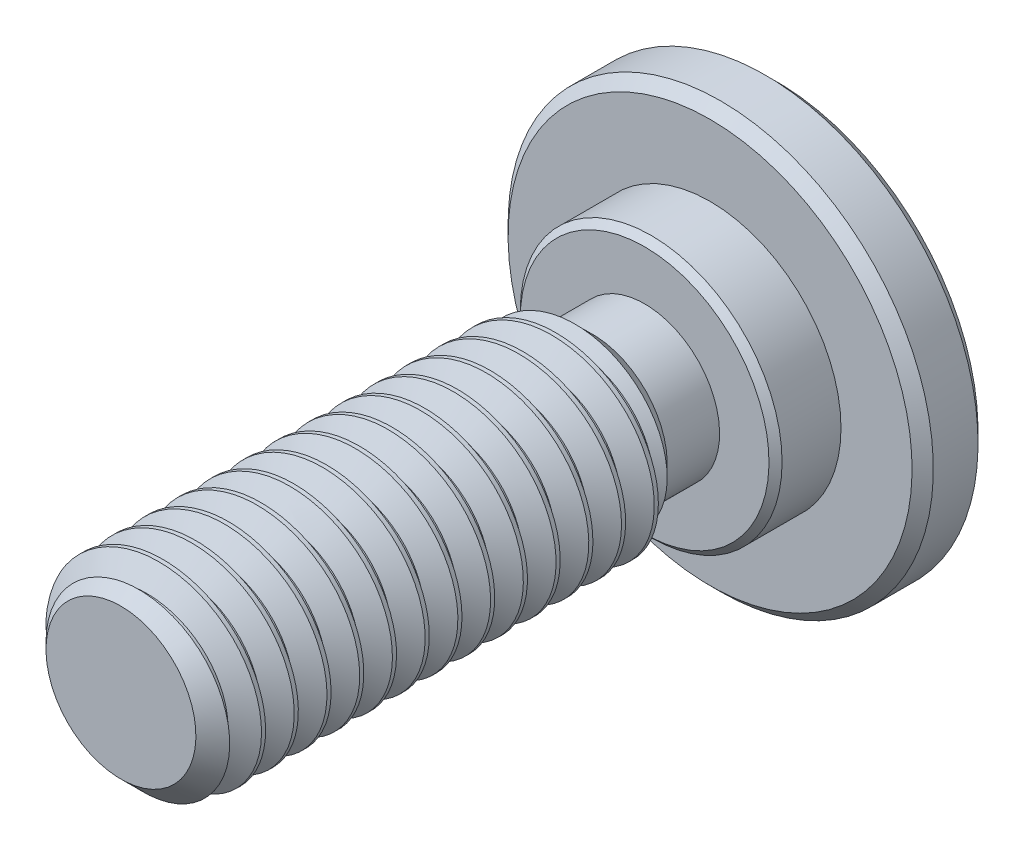
SolidWorks part; units mm, degrees
other "DetailItem1"
ref_plane "Front Plane" through (0, 0, 0) normal (0, 0, 1) x (1, 0, 0)
ref_plane "Top Plane" through (0, 0, 0) normal (0, 1, 0) x (1, 0, 0)
ref_plane "Right Plane" through (0, 0, 0) normal (1, 0, 0) x (0, 0, -1)
sketch "Sketch1" plane through (0, 0, 0) normal (1, 0, 0) x (0, 0, -1)
  line L0 (0, 0) -> (-14.2875, 0) construction
  line L1 (0, 0) -> (1.6002, 0) construction
  line L2 (1.6002, 5.1562) -> (1.6002, -5.1562) construction
  line L3 (-14.2875, 2.413) -> (-14.2875, -2.413) construction
  line L4 (0, 3.175) -> (0, -3.175) construction
  line L5 (-14.2875, 2.413) -> (-13.4938, 2.413) construction
  line L6 (1.6002, 1.1906) -> (1.6002, -1.1906) construction
  line L7 (0, 3.175) -> (-1.5875, 3.175) construction
  line L8 (-1.5875, 3.175) -> (-1.5875, 1.8177) construction
  line L9 (-1.5875, 1.8177) -> (-2.8575, 1.8177) construction
  line L10 (-2.8575, 1.8177) -> (-3.4528, 2.413) construction
  point P2 (-11.5094, -2.413)
  point P4 (-1.5875, 0)
  point P8 (1.6002, 0)
  point P11 (-14.2875, 0)
  point P14 (0, 0)
  point P19 (1.6002, 0)
  dimension "Thread Diameter" = 4.826
  dimension "Head Diameter" = 10.3124
  dimension "Head Height" = 1.6002
  dimension "Shoulder Diameter" = 6.35
  dimension "Shoulder Length" = 1.5875
  dimension "Thread Pitch" = 0.7937
  dimension "Drive Size" = 2.3813
  dimension "D1" = 2.7781
  dimension "D3" = 3.6354
  dimension "Undercut Length" = 1.27
  dimension "D2" = 45
  dimension "Length" = 12.7
sketch "Sketch13" plane through (0, 0, 0) normal (1, 0, 0) x (0, 0, -1)
  line L0 (1.6002, 5.1562) -> (0, 5.1562)
  line L1 (0, 5.1562) -> (0, 3.175)
  line L3 (-14.2875, 2.413) -> (-14.2875, 0)
  line L4 (-14.2875, 0) -> (1.6002, 0)
  line L5 (1.6002, 0) -> (1.6002, 5.1562)
  line L6 (-2.8575, 1.8177) -> (-3.4528, 2.413) construction
  line L7 (-1.5875, 1.8177) -> (-2.8575, 1.8177) construction
  line L8 (-1.5875, 3.175) -> (-1.5875, 1.8177) construction
  line L9 (0, 3.175) -> (-1.5875, 3.175) construction
  line L10 (-2.8575, 1.8177) -> (-3.4528, 2.413)
  line L11 (-1.5875, 1.8177) -> (-2.8575, 1.8177)
  line L12 (-1.5875, 3.175) -> (-1.5875, 1.8177)
  line L13 (0, 3.175) -> (-1.5875, 3.175)
  line L14 (-3.4528, 2.413) -> (-14.2875, 2.413)
revolve "Revolve1" add sketch "Sketch13" angle 360 about L4
sketch "Sketch2" plane through (0, 0, 14.2875) normal (0, 0, 1) x (1, 0, 0)
  circle A2 centre (0, 0) radius 2.413
chamfer "Chamfer2" distance 0.5953 angle 45 1 edges at (0, -2.413, 14.2875)
sketch "Sketch3" plane through (0, 0, 0) normal (1, 0, 0) x (0, 0, -1)
  line L0 (-14.2379, 2.4989) -> (-15.0316, 2.4989) construction
  line L1 (-15.0316, 2.4989) -> (-14.6348, 1.8115) construction
  line L2 (-14.6348, 1.8115) -> (-14.2379, 2.4989) construction
  line L4 (-14.2875, 2.413) -> (-14.982, 2.413) construction
  line L5 (-14.6348, 2.4989) -> (-14.6348, 2.413) construction
  line L6 (-15.0068, 2.456) -> (-14.2627, 2.456)
  line L7 (-14.2627, 2.456) -> (-15.0068, 2.456) construction
  line L8 (-14.5852, 1.8974) -> (-14.6844, 1.8974) construction
  line L9 (-14.6348, 1.8974) -> (-14.6348, 1.8115) construction
  line L10 (-14.2627, 2.456) -> (-14.5852, 1.8974)
  line L11 (-14.5852, 1.8974) -> (-14.6844, 1.8974)
  line L12 (-14.6844, 1.8974) -> (-15.0068, 2.456)
  point P16 (-14.6348, 2.456)
  dimension "D1" = 0.7937
  dimension "D2" = 0.0992
sketch "Sketch7" plane through (0, 0, -1.6002) normal (0, 0, -1) x (-1, 0, 0)
  line L1 (0, 1.3748) -> (-1.1906, 0.6874)
  line L2 (-1.1906, 0.6874) -> (-1.1906, -0.6874)
  line L3 (-1.1906, -0.6874) -> (0, -1.3748)
  line L4 (0, -1.3748) -> (1.1906, -0.6874)
  line L5 (1.1906, -0.6874) -> (1.1906, 0.6874)
  line L6 (1.1906, 0.6874) -> (0, 1.3748)
  circle A0 centre (0, 0) radius 1.1906 construction
extrude "Cut-Extrude1" cut sketch "Sketch7" against normal blind 1.7859
chamfer "Chamfer1" distance 0.2578 angle 45 2 edges at (0, -5.1562, -1.6002) (0, -5.1562, 0)
sketch "Sketch8" plane through (0, 0, -1.6002) normal (0, 0, -1) x (-1, 0, 0)
  circle A0 centre (0, 0) radius 1.3748
extrude "Cut-Extrude2" cut sketch "Sketch8" against normal through all draft 45
chamfer "Chamfer3" distance 0.1588 angle 45 1 edges at (0, -3.175, 1.5875)
curve "Helix/Spiral1" pitch 0.7937 height 12.446 turns 15.68 parameters "pitch"=0.7937
sweep "Cut-Sweep1" cut profiles "Sketch3" path "Helix/Spiral1"
equation "\"D3@Helix/Spiral1\"=\"Length@Sketch1\"- .01"
equation "\"D1@Cut-Extrude1\" = \"Drive Size@Sketch1\" * .75"
equation "\"D1@Chamfer1\"=\"Head Diameter@Sketch1\" * .025"
equation "\"D1@Chamfer2\"=\"pitch@Helix/Spiral1\"*.750"
equation "\"D1@Sketch3\" = \"Thread Pitch@Sketch1\""
equation "\"D2@Sketch3\"=\"D1@Sketch3\"/ 1/8"
equation "\"pitch@Helix/Spiral1\" = \"Thread Pitch@Sketch1\""
equation "\"D1@Sketch1\" = \"Thread Pitch@Sketch1\" * 3.5"
equation "\"D3@Sketch1\"=\"Thread Diameter@Sketch1\" -(\"Thread Pitch@Sketch1\"*1.5)"
equation "\"D1@Chamfer3\"=\"Shoulder Diameter@Sketch1\"*.025"
